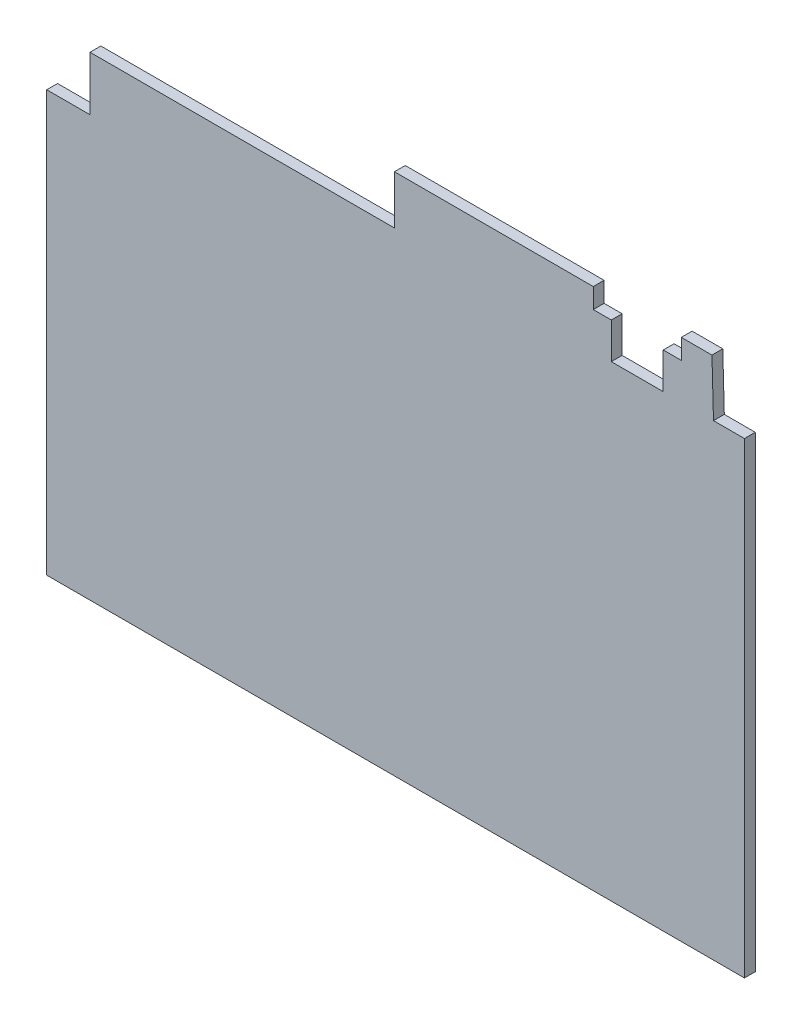
SolidWorks part; units mm, degrees
material "ABS"
ref_plane "Front Plane" through (0, 0, 0) normal (0, 0, 1) x (1, 0, 0)
ref_plane "Top Plane" through (0, 0, 0) normal (0, 1, 0) x (1, 0, 0)
ref_plane "Right Plane" through (0, 0, 0) normal (1, 0, 0) x (0, 0, -1)
sketch "Sketch1" plane through (0, 0, 0) normal (0, 0, 1) x (1, 0, 0)
  line L0 (28.5714, 236.0602) -> (28.5714, 237.0518)
  line L1 (28.5714, 277.1048) -> (28.5714, -22.8952) construction
  line L2 (28.5714, 237.0518) -> (5.4155, 237.0518)
  line L3 (5.4155, 237.0518) -> (4.5714, 268.1048)
  line L4 (4.5714, 268.1048) -> (-12.4286, 268.1048)
  line L5 (-12.4286, 268.1048) -> (-12.4286, 237.0518)
  line L6 (-12.4286, 237.0518) -> (-38.2166, 237.0518)
  line L7 (-38.2166, 237.0518) -> (-38.2166, 268.1048)
  line L8 (-221.4286, 268.1048) -> (28.5714, 268.1048) construction
  line L9 (-38.2166, 268.1048) -> (-171.4286, 268.1048)
  line L10 (-171.4286, 268.1048) -> (-171.4286, 241.1048)
  line L11 (-171.4286, 241.1048) -> (-370.1235, 241.1048)
  line L12 (-370.1235, 241.1048) -> (-370.1235, -22.8952)
  line L13 (-370.1235, -22.8952) -> (28.5714, -22.8952)
  line L14 (28.5714, -22.8952) -> (28.5714, 236.0602)
extrude "Boss-Extrude1" add sketch "Sketch1" along normal blind 6
sketch "Sketch2" plane through (0, 0, 6) normal (0, 0, 1) x (1, 0, 0)
  line L1 (-370.1235, 241.1048) -> (-340.1235, 241.1048)
  line L2 (-370.1235, 241.1048) -> (-370.1235, 211.1048)
  line L3 (-370.1235, 211.1048) -> (-340.1235, 211.1048)
  line L4 (-340.1235, 241.1048) -> (-340.1235, 211.1048)
  dimension "D1" = 30
  dimension "D2" = 30
extrude "Cut-Extrude1" cut sketch "Sketch2" against normal blind 10
sketch "Sketch3" plane through (0, 0, 6) normal (0, 0, 1) x (1, 0, 0)
  line L0 (28.5714, -22.8952) -> (28.5714, 237.0518) construction
  line L1 (-370.1235, -22.8952) -> (28.5714, -22.8952)
  line L2 (-370.1235, -22.8952) -> (-370.1235, -21.8952)
  line L3 (-370.1235, -21.8952) -> (28.5714, -21.8952)
  line L4 (28.5714, -22.8952) -> (28.5714, -21.8952)
  dimension "D1" = 1
extrude "Cut-Extrude2" cut sketch "Sketch3" against normal blind 10
sketch "Sketch4" plane through (0, 0, 6) normal (0, 0, 1) x (1, 0, 0)
  line L0 (-370.1235, 211.1048) -> (-340.1235, 211.1048) construction
  line L1 (-370.1235, -21.8952) -> (-364.1235, -21.8952)
  line L2 (-370.1235, -21.8952) -> (-370.1235, 211.1048)
  line L3 (-370.1235, 211.1048) -> (-364.1235, 211.1048)
  line L4 (-364.1235, -21.8952) -> (-364.1235, 211.1048)
  line L5 (28.5714, 237.0518) -> (5.4155, 237.0518) construction
  line L6 (28.5714, -21.8952) -> (22.5714, -21.8952)
  line L7 (28.5714, -21.8952) -> (28.5714, 237.0518)
  line L8 (28.5714, 237.0518) -> (22.5714, 237.0518)
  line L9 (22.5714, -21.8952) -> (22.5714, 237.0518)
  dimension "D1" = 6
  dimension "D2" = 6
extrude "Cut-Extrude3" cut sketch "Sketch4" against normal blind 10
sketch "Sketch5" plane through (0, 0, 6) normal (0, 0, 1) x (1, 0, 0)
  line L0 (-38.2166, 268.1048) -> (-171.4286, 268.1048) construction
  line L1 (-38.2166, 237.0518) -> (-61.2166, 237.0518)
  line L2 (-38.2166, 237.0518) -> (-38.2166, 268.1048)
  line L3 (-38.2166, 268.1048) -> (-61.2166, 268.1048)
  line L4 (-61.2166, 237.0518) -> (-61.2166, 268.1048)
  dimension "D1" = 23
extrude "Cut-Extrude4" cut sketch "Sketch5" against normal blind 10
sketch "Sketch6" plane through (0, 0, 6) normal (0, 0, 1) x (1, 0, 0)
  line L1 (-12.4286, 237.0518) -> (-22.4286, 237.0518)
  line L2 (-12.4286, 237.0518) -> (-12.4286, 257.0518)
  line L3 (-12.4286, 257.0518) -> (-22.4286, 257.0518)
  line L4 (-22.4286, 237.0518) -> (-22.4286, 257.0518)
  line L5 (-61.2166, 237.0518) -> (-51.2166, 237.0518)
  line L6 (-61.2166, 237.0518) -> (-61.2166, 257.0518)
  line L7 (-61.2166, 257.0518) -> (-51.2166, 257.0518)
  line L8 (-51.2166, 237.0518) -> (-51.2166, 257.0518)
  dimension "D1" = 20
  dimension "D2" = 20
  dimension "D3" = 10
  dimension "D4" = 10
extrude "Boss-Extrude2" add sketch "Sketch6" against normal up to vertex (6 mm away) up to point (-171.4286, 241.1048, 0)
